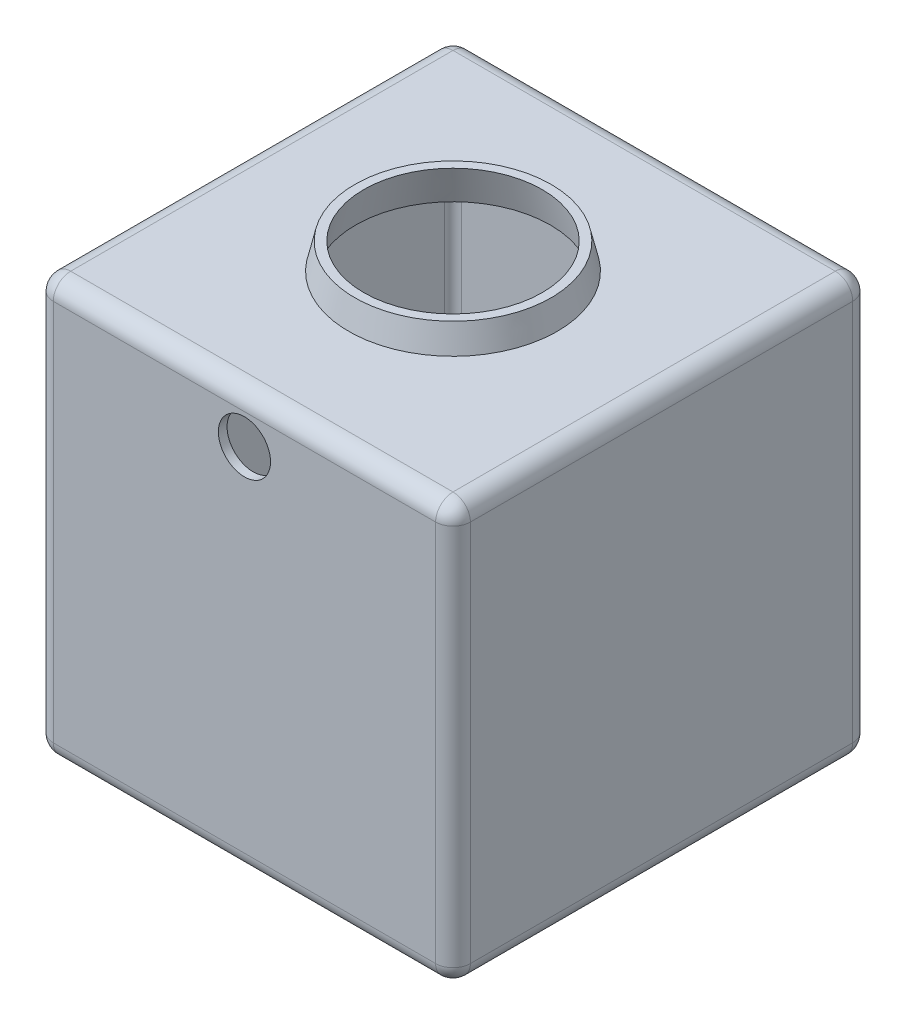
SolidWorks part; units mm, degrees
ref_plane "Front Plane" through (0, 0, 0) normal (0, 0, 1) x (1, 0, 0)
ref_plane "Top Plane" through (0, 0, 0) normal (0, 1, 0) x (1, 0, 0)
ref_plane "Right Plane" through (0, 0, 0) normal (1, 0, 0) x (0, 0, -1)
sketch "Sketch1" plane through (0, 0, 0) normal (0, 0, 1) x (1, 0, 0)
  line L1 (0, 0) -> (480, 0)
  line L2 (0, 0) -> (0, -480)
  line L3 (0, -480) -> (480, -480)
  line L4 (480, 0) -> (480, -480)
  dimension "D1" = 480
  dimension "D2" = 480
extrude "Boss-Extrude1" add sketch "Sketch1" along normal mid plane 480
fillet "Fillet1" radius 20 12 edges at (0, 0, 0) (0, -480, 0) (240, 0, 240) (240, -480, 240) (0, -240, 240) (240, -480, -240) (240, 0, -240) (0, -240, -240) (480, -480, 0) (480, -240, 240) (480, 0, 0) (480, -240, -240)
sketch "Sketch2" plane through (0, 0, 0) normal (0, 0, 1) x (1, 0, 0)
  line L0 (20, 0) -> (460, 0) construction
  line L1 (240, 0) -> (360, 0)
  line L2 (240, 0) -> (240, 30)
  line L3 (240, 30) -> (353, 30)
  line L5 (20, -240) -> (460, -240) construction
  line L12 (20, -20) -> (20, -460) construction
  line L13 (460, -460) -> (460, -20) construction
  line L18 (360, 0) -> (353, 30)
  line L19 (360, -480) -> (353, -510)
  line L20 (240, -510) -> (353, -510)
  line L21 (240, -480) -> (240, -510)
  line L22 (240, -480) -> (360, -480)
  dimension "D1" = 113
  dimension "D2" = 30
  dimension "D3" = 120
revolve "Revolve1" add sketch "Sketch2" angle 360 about L2
shell "Shell1" thickness 10 removed face at (240, -510, -113) removed face at (240, 30, -113)
sketch "Sketch3" plane through (0, 0, 0) normal (0, 0, 1) x (1, 0, 0)
  line L0 (460, -20) -> (20, -20) construction
  circle A0 centre (240, -55) radius 30
  point P4 (0, 0)
  point P5 (240, -20)
  dimension "D1" = 60
  dimension "D2" = 35
extrude "Cut-Extrude1" cut sketch "Sketch3" against normal through all both and the other way through all
